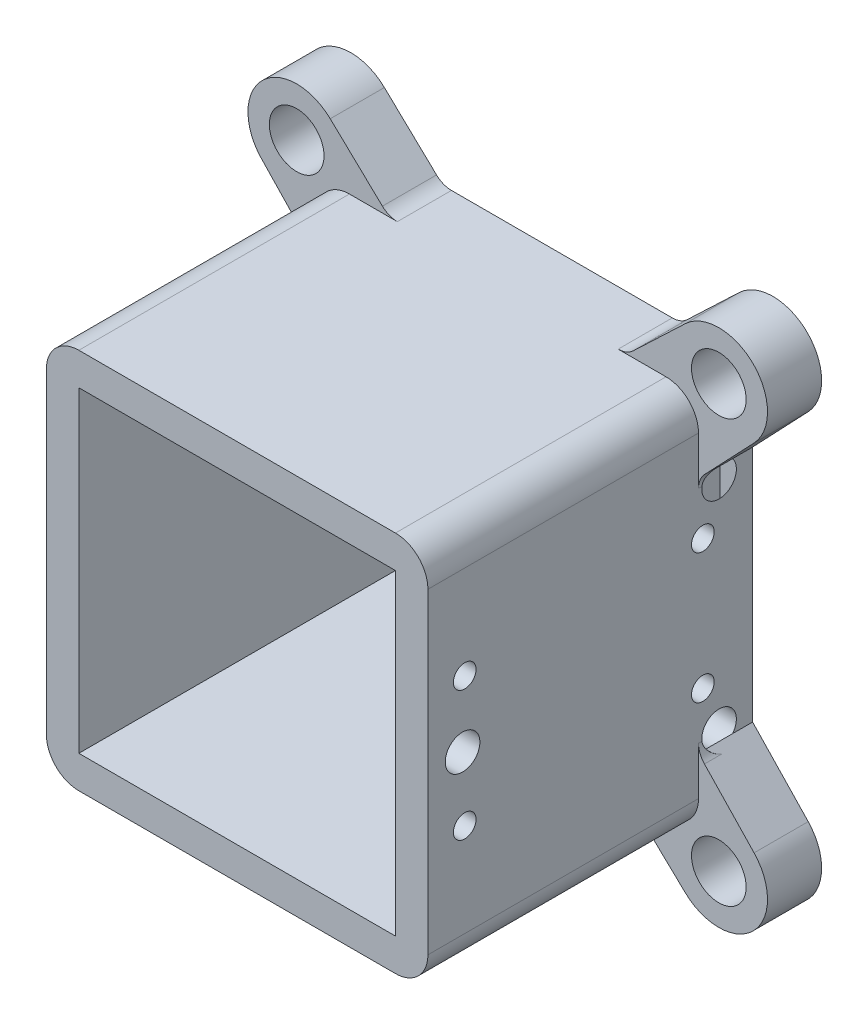
SolidWorks part; units mm, degrees
ref_plane "Front Plane" through (0, 0, 0) normal (0, 0, 1) x (1, 0, 0)
ref_plane "Top Plane" through (0, 0, 0) normal (0, 1, 0) x (1, 0, 0)
ref_plane "Right Plane" through (0, 0, 0) normal (1, 0, 0) x (0, 0, -1)
sketch "Sketch1" plane through (0, 0, 0) normal (0, 0, 1) x (1, 0, 0)
  line L0 (-17.625, 0) -> (17.625, 0) construction
  line L1 (0, 17.625) -> (0, -17.625) construction
  line L2 (-14.625, 14.625) -> (14.625, 14.625)
  line L3 (-14.625, 14.625) -> (-14.625, -14.625)
  line L4 (-14.625, -14.625) -> (14.625, -14.625)
  line L5 (14.625, 14.625) -> (14.625, -14.625)
  line L6 (-17.625, 17.625) -> (17.625, 17.625) construction
  line L7 (-17.625, 17.625) -> (-17.625, -17.625) construction
  line L8 (-17.625, -17.625) -> (17.625, -17.625) construction
  line L9 (17.625, 17.625) -> (17.625, -17.625) construction
  line L11 (-19.5, 19.5) -> (19.5, 19.5) construction
  line L12 (-17.625, 11) -> (-17.625, -11)
  line L13 (17.625, 11) -> (17.625, -11)
  line L14 (-11, 17.625) -> (11, 17.625)
  line L15 (-11, -17.625) -> (11, -17.625)
  line L16 (-17.625, 11) -> (-22.7604, 16.3984)
  line L17 (-16.3984, 22.7604) -> (-11, 17.625)
  line L18 (11, 17.625) -> (16.3984, 22.7604)
  line L19 (22.7604, 16.3984) -> (17.625, 11)
  line L20 (22.7604, -16.3984) -> (17.625, -11)
  line L21 (16.3984, -22.7604) -> (11, -17.625)
  line L22 (-22.7604, -16.3984) -> (-17.625, -11)
  line L23 (-16.3984, -22.7604) -> (-11, -17.625)
  line L24 (-19.5, 19.5) -> (-19.5, -19.5) construction
  line L25 (-19.5, -19.5) -> (19.5, -19.5) construction
  line L26 (19.5, 19.5) -> (19.5, -19.5) construction
  arc A0 (-16.3984, 22.7604) -> (-22.7604, 16.3984) centre (-19.5, 19.5) ccw
  arc A1 (22.7604, 16.3984) -> (16.3984, 22.7604) centre (19.5, 19.5) ccw
  arc A2 (16.3984, -22.7604) -> (22.7604, -16.3984) centre (19.5, -19.5) ccw
  arc A4 (-22.7604, -16.3984) -> (-16.3984, -22.7604) centre (-19.5, -19.5) ccw
  circle A5 centre (-19.5, 19.5) radius 2.525
  circle A6 centre (19.5, 19.5) radius 2.525
  circle A7 centre (19.5, -19.5) radius 2.525
  circle A8 centre (-19.5, -19.5) radius 2.525
  dimension "D6" = 9
  dimension "4.2" = 5.05
  dimension "D1" = 3
  dimension "D4" = 3
  dimension "D2" = 3
  dimension "D3" = 3
  dimension "D5" = 29.25
  dimension "D7" = 22
  dimension "D8" = 11
  dimension "D9" = 11
  dimension "D10" = 11
  dimension "D11" = 11
  dimension "D13" = 39
  dimension "D14" = 19.5
  dimension "D15" = 19.5
  dimension "D12" = 136.43
extrude "Boss-Extrude1" add sketch "Sketch1" along normal blind 5
sketch "Sketch2" plane through (0, 0, 5) normal (0, 0, 1) x (1, 0, 0)
  line L1 (-14.625, 14.625) -> (14.625, 14.625)
  line L2 (-14.625, 14.625) -> (-14.625, -14.625)
  line L3 (-14.625, -14.625) -> (14.625, -14.625)
  line L4 (14.625, 14.625) -> (14.625, -14.625)
  line L5 (-14.625, 17.625) -> (14.625, 17.625)
  line L6 (-17.625, 14.625) -> (-17.625, -14.625)
  line L7 (-14.625, -17.625) -> (14.625, -17.625)
  line L8 (17.625, 14.625) -> (17.625, -14.625)
  arc A0 (17.625, 14.625) -> (14.625, 17.625) centre (14.625, 14.625) ccw
  arc A1 (14.625, -17.625) -> (17.625, -14.625) centre (14.625, -14.625) ccw
  arc A2 (-14.625, -17.625) -> (-17.625, -14.625) centre (-14.625, -14.625) cw
  arc A3 (-14.625, 17.625) -> (-17.625, 14.625) centre (-14.625, 14.625) ccw
  point P12 (17.625, 17.625)
  point P15 (17.625, -17.625)
  point P20 (-17.625, 17.625)
  dimension "D5" = 3
  dimension "D1" = 3
  dimension "D2" = 3
  dimension "D3" = 3
  dimension "D4" = 3
extrude "Boss-Extrude2" add sketch "Sketch2" along normal blind 25
sketch "Sketch4" plane through (17.625, 0, 0) normal (1, 0, 0) x (0, 0, -1)
  line L0 (-26.6, 6) -> (-4.6, 6) construction
  line L1 (-26.6, -6) -> (-26.6, 6) construction
  line L2 (-4.6, 6) -> (-4.6, -6) construction
  line L3 (-26.6, -6) -> (-4.6, -6) construction
  point P0 (-26.6, 6)
  point P1 (-4.6, -6)
  point P2 (-26.6, -6)
  point P3 (-4.6, 6)
  dimension "D1" = 22
  dimension "D2" = 12
  dimension "D3" = 6
  dimension "D4" = 4.6
hole_wizard "M2 Hole Bottom" positions "Sketch4" profile "Sketch5" hole size "Ø1.0" standard "ISO"
sketch "Sketch5" plane through (17.625, 6, 26.6) normal (0, 1, 0) x (0, 0, -1)
  line L0 (0, 0) -> (0, 3)
  line L1 (0, 3) -> (1.05, 3)
  line L2 (1.05, 3) -> (1.05, 0)
  line L5 (1.05, 0) -> (0, 0)
  line L11 (0, -6.35) -> (0, 107.95) construction
  dimension "Thru Hole Dia." = 2.1
  dimension "Thru Hole Depth" = 3
sketch "Sketch6" plane through (17.625, 0, 0) normal (1, 0, 0) x (0, 0, -1)
  line L0 (0, 0) -> (-36.0191, 0) construction
  line L2 (-26.8, 10) -> (-3.1, 10) construction
  line L3 (-26.8, 10) -> (-26.8, -10) construction
  line L4 (-26.8, -10) -> (-3.1, -10) construction
  line L5 (-3.1, 10) -> (-3.1, -10) construction
  point P11 (-26.8, 0)
  point P18 (-3.1, 10)
  point P21 (-3.1, -10)
  dimension "D1" = 23.7
  dimension "D2" = 20
  dimension "D3" = 10
  dimension "D4" = 3.1
hole_wizard "M3 Hole Bottom" positions "Sketch6" profile "Sketch7" hole size "Ø1.0" standard "ISO"
sketch "Sketch7" plane through (17.625, -10, 3.1) normal (0, 1, 0) x (0, 0, -1)
  line L0 (0, 0) -> (0, 3)
  line L1 (0, 3) -> (1.6, 3)
  line L2 (1.6, 3) -> (1.6, 0)
  line L5 (1.6, 0) -> (0, 0)
  line L11 (0, -6.35) -> (0, 107.95) construction
  dimension "Thru Hole Dia." = 3.2
  dimension "Thru Hole Depth" = 3
fillet "Fillet2" radius 2 8 edges at (11, 17.625, 2.5) (-11, 17.625, 2.5) (-17.625, 11, 2.5) (-17.625, -11, 2.5) (-11, -17.625, 2.5) (11, -17.625, 2.5) (17.625, -11, 4.6745) (17.625, 11, 4.6745)
sketch "Sketch8" plane through (-17.625, 0, 0) normal (-1, 0, 0) x (0, 0, 1)
  line L0 (0, 0) -> (30, 0) construction
  line L1 (30, 14.625) -> (30, -14.625) construction
  point P4 (2, 6)
  point P5 (2, -6)
  point P6 (0, 0)
  point P8 (0, 0)
  point P9 (0, 0)
  point P10 (4.5432, 6)
  dimension "D1" = 12
  dimension "D2" = 6
  dimension "D3" = 2
hole_wizard "M2 Hole Top" positions "Sketch8" profile "Sketch9" hole size "Ø1.0" standard "ISO"
sketch "Sketch9" plane through (-17.625, -6, 2) normal (0, 1, 0) x (0, 0, 1)
  line L0 (0, 0) -> (0, 3)
  line L1 (0, 3) -> (1.05, 3)
  line L2 (1.05, 3) -> (1.05, 0)
  line L5 (1.05, 0) -> (0, 0)
  line L11 (0, -6.35) -> (0, 107.95) construction
  dimension "Thru Hole Dia." = 2.1
  dimension "Thru Hole Depth" = 3
equation "\"D14@Sketch1\"=39/2"
equation "\"D15@Sketch1\"=39/2"
equation "\"D1@Boss-Extrude2\"=30-5mm"
equation "\"D3@Sketch4\"=12/2"
equation "\"D3@Sketch6\"=20/2"
equation "\"external_wo_arms\" = 22"
equation "\"D7@Sketch1\"=\"external_wo_arms\""
equation "\"D11@Sketch1\"=\"external_wo_arms\"/2"
equation "\"D9@Sketch1\"=\"external_wo_arms\"/2"
equation "\"D8@Sketch1\"=\"external_wo_arms\"/2"
equation "\"D10@Sketch1\"=\"external_wo_arms\"/2"
equation "\"wall_thickness\"= 3mm"
equation "\"D3@Sketch1\"=\"wall_thickness\""
equation "\"D2@Sketch1\"=\"wall_thickness\""
equation "\"D4@Sketch1\"=\"wall_thickness\""
equation "\"D1@Sketch1\"=\"wall_thickness\""
